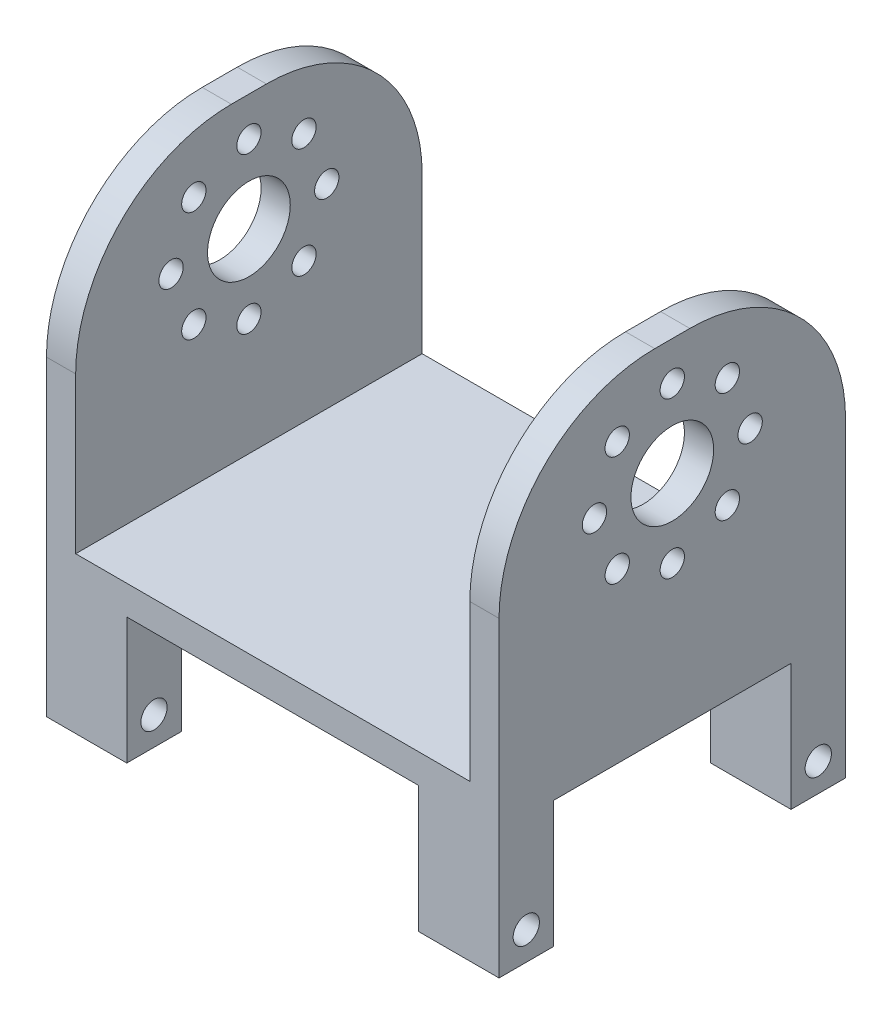
SolidWorks part; units mm, degrees
ref_plane "Front Plane" through (0, 0, 0) normal (0, 0, 1) x (1, 0, 0)
ref_plane "Top Plane" through (0, 0, 0) normal (0, 1, 0) x (1, 0, 0)
ref_plane "Right Plane" through (0, 0, 0) normal (1, 0, 0) x (0, 0, -1)
sketch "Sketch1" plane through (0, 0, 0) normal (0, 1, 0) x (1, 0, 0)
  line L1 (-23.25, -17.8) -> (23.25, -17.8)
  line L2 (-23.25, -17.8) -> (-23.25, 17.8)
  line L3 (-23.25, 17.8) -> (23.25, 17.8)
  line L4 (23.25, -17.8) -> (23.25, 17.8)
  line L5 (-23.25, -17.8) -> (23.25, 17.8) construction
  line L6 (-23.25, 17.8) -> (23.25, -17.8) construction
  point P0 (0, 0)
  dimension "D1" = 46.5
  dimension "D2" = 35.6
extrude "Boss-Extrude1" add sketch "Sketch1" along normal blind 2
sketch "Sketch2" plane through (0, 2, 0) normal (0, 1, 0) x (1, 0, 0)
  line L0 (-23.25, -17.8) -> (23.25, -17.8) construction
  line L1 (-23.25, 17.8) -> (-20.25, 17.8)
  line L2 (-23.25, 17.8) -> (-23.25, -17.8)
  line L3 (-23.25, -17.8) -> (-20.25, -17.8)
  line L4 (-20.25, 17.8) -> (-20.25, -17.8)
  line L6 (23.25, 17.8) -> (20.25, 17.8)
  line L7 (23.25, 17.8) -> (23.25, -17.8)
  line L8 (23.25, -17.8) -> (20.25, -17.8)
  line L9 (20.25, 17.8) -> (20.25, -17.8)
  dimension "D1" = 3
  dimension "D2" = 3
extrude "Boss-Extrude2" add sketch "Sketch2" along normal blind 50
sketch "Sketch3" plane through (23.25, 0, 0) normal (1, 0, 0) x (0, 0, -1)
  line L0 (-17.8, 52) -> (17.8, 52) construction
  circle A0 centre (0, 40) radius 4.25
  dimension "D1" = 8.5
  dimension "D2" = 12
extrude "Cut-Extrude1" cut sketch "Sketch3" against normal through all
sketch "Sketch5" plane through (23.25, 0, 0) normal (1, 0, 0) x (0, 0, -1)
  circle A0 centre (0, 40) radius 8
  dimension "D1" = 16
sketch "Sketch6" plane through (23.25, 0, 0) normal (1, 0, 0) x (0, 0, -1)
  circle A0 centre (0, 32) radius 1.25
  circle A1 centre (0, 40) radius 8 construction
  circle A2 centre (-5.6569, 34.3431) radius 1.25
  circle A3 centre (-8, 40) radius 1.25
  circle A4 centre (-5.6569, 45.6569) radius 1.25
  circle A5 centre (0, 48) radius 1.25
  circle A6 centre (5.6569, 45.6569) radius 1.25
  circle A7 centre (8, 40) radius 1.25
  circle A8 centre (5.6569, 34.3431) radius 1.25
  point P21 (0, 40)
  dimension "D1" = 2.5
  dimension "D3" = 8
  dimension "D2" = 8
extrude "Cut-Extrude3" cut sketch "Sketch6" against normal through all
fillet "Fillet5" radius 16 4 edges at (-21.75, 52, 17.8) (21.75, 52, 17.8) (21.75, 52, -17.8) (-21.75, 52, -17.8)
extrude "Cut-Extrude6" cut sketch "Sketch1<2>" along normal blind 20
sketch "Sketch1<2>" plane through (0, 0, 0) normal (0, 1, 0) x (1, 0, 0) same geometry as "Sketch1"
sketch "Sketch8" plane through (0, 20, 0) normal (0, -1, 0) x (1, 0, 0)
  line L1 (-23.25, 17.8) -> (23.25, 17.8)
  line L2 (-23.25, 17.8) -> (-23.25, -17.8)
  line L3 (-23.25, -17.8) -> (23.25, -17.8)
  line L4 (23.25, 17.8) -> (23.25, -17.8)
extrude "Boss-Extrude3" add sketch "Sketch8" along normal blind 3
sketch "Sketch9" plane through (23.25, 0, 0) normal (1, 0, 0) x (0, 0, -1)
  line L1 (-17.8, 17) -> (17.8, 17)
  line L2 (-17.8, 17) -> (-17.8, 4)
  line L3 (-17.8, 4) -> (17.8, 4)
  line L4 (17.8, 17) -> (17.8, 4)
  dimension "D1" = 13
  dimension "D2" = 35.6
extrude "Boss-Extrude4" add sketch "Sketch9" against normal up to surface (46.5 mm away) up to face at (-23.25, 40, -4.25)
sketch "Sketch12" plane through (0, 0, -17.8) normal (0, 0, -1) x (-1, 0, 0)
  line L0 (23.25, 4) -> (-23.25, 4) construction
  line L1 (-15, 4) -> (15, 4)
  line L2 (-15, 4) -> (-15, 17)
  line L3 (-15, 17) -> (15, 17)
  line L4 (15, 4) -> (15, 17)
  line L5 (20.25, 20) -> (-20.25, 20) construction
  line L6 (23.25, 36) -> (23.25, 4) construction
  dimension "D1" = 3
  dimension "D2" = 30
  dimension "D3" = 8.25
extrude "Cut-Extrude9" cut sketch "Sketch12" against normal through all
sketch "Sketch13" plane through (15, 0, 0) normal (-1, 0, 0) x (0, 0, 1)
  line L0 (-17.8, 4) -> (17.8, 4) construction
  line L1 (-12.2, 4) -> (12.2, 4)
  line L2 (-12.2, 4) -> (-12.2, 17)
  line L3 (-12.2, 17) -> (12.2, 17)
  line L4 (12.2, 4) -> (12.2, 17)
  line L5 (17.8, 36) -> (17.8, 4) construction
  line L6 (-17.8, 36) -> (-17.8, 4) construction
  dimension "D1" = 13
  dimension "D2" = 5.6
  dimension "D3" = 5.6
extrude "Cut-Extrude10" cut sketch "Sketch13" along normal through all and the other way through all
sketch "Sketch15" plane through (-23.25, 0, 0) normal (-1, 0, 0) x (0, 0, 1)
  line L0 (12.2, 17) -> (-12.2, 17) construction
  line L1 (-17.8, 36) -> (-17.8, 4) construction
  line L2 (0, -25.575) -> (0, 25.575) construction
  circle A0 centre (-15, 6.9) radius 1.35
  circle A1 centre (15, 6.9) radius 1.35
  dimension "D1" = 2.7
  dimension "D2" = 10.1
  dimension "D3" = 2.8
extrude "Cut-Extrude11" cut sketch "Sketch15" against normal through all
